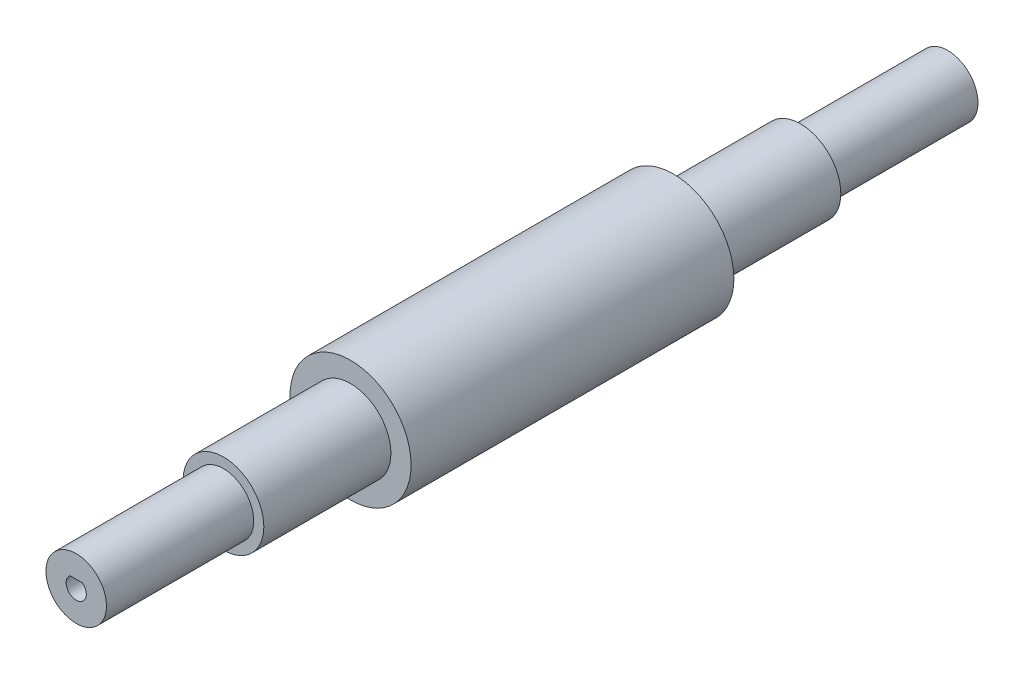
SolidWorks part; units mm, degrees
note: The reader was unsure of these and kept them because the rebuilt part matched: shared geometry of "Esquisse1<10>", "Esquisse1<7>", "Esquisse1<8>", "Esquisse1<11>".
ref_plane "Plan de face" through (0, 0, 0) normal (0, 0, 1) x (1, 0, 0)
ref_plane "Plan de dessus" through (0, 0, 0) normal (0, 1, 0) x (1, 0, 0)
ref_plane "Plan de droite" through (0, 0, 0) normal (1, 0, 0) x (0, 0, -1)
sketch "Esquisse1" plane through (0, 0, 0) normal (0, 0, 1) x (1, 0, 0)
  line L0 (-48.5255, 0) -> (60.6197, 0) construction
  line L1 (0, 41.1471) -> (0, -40.7888) construction
  line L2 (-1.5, 2) -> (1.5, 2)
  circle A0 centre (0, 0) radius 15
  circle A15 centre (0, 0) radius 10
  circle A26 centre (0, 0) radius 7.5
  arc A27 (-1.5, 2) -> (1.5, 2) centre (0, 0) ccw
  point P29 (0, 0)
  point P30 (-8.6942, -5.0196)
  dimension "D1" = 30
  dimension "D2" = 20
  dimension "D3" = 2
  dimension "D8" = 15
  dimension "D9" = 5
extrude "Boss.-Extru.1" add sketch "Esquisse1" along normal mid plane 80 contours A0
extrude "Boss.-Extru.5" add sketch "Esquisse1<10>" along normal blind 31.5 from offset 40 contours A15
sketch "Esquisse1<10>" plane through (0, 0, 0) normal (0, 0, 1) x (1, 0, 0) same geometry as "Esquisse1"
extrude "Boss.-Extru.3" add sketch "Esquisse1<7>" along normal blind 36.5 from offset 71.5 separate body contours A26 | A27 L2
sketch "Esquisse1<7>" plane through (0, 0, 0) normal (0, 0, 1) x (1, 0, 0) same geometry as "Esquisse1"
extrude "Boss.-Extru.4" add sketch "Esquisse1<8>" against normal blind 36.5 from offset 71.5 contours A26 | A27 L2 offset against normal yes
sketch "Esquisse1<8>" plane through (0, 0, 0) normal (0, 0, 1) x (1, 0, 0) same geometry as "Esquisse1"
extrude "Boss.-Extru.6" add sketch "Esquisse1<11>" against normal blind 31.5 from offset 40 contours A15 offset against normal yes
sketch "Esquisse1<11>" plane through (0, 0, 0) normal (0, 0, 1) x (1, 0, 0) same geometry as "Esquisse1"
sketch "Esquisse4" plane through (0, 0, 40) normal (0, 0, 1) x (1, 0, 0)
  circle A1 centre (0, 0) radius 15
  circle A2 centre (0, 0) radius 15
  dimension "D1" = 0
curve "Hélice/Spirale1" pitch 160 height 80 turns 0.5
